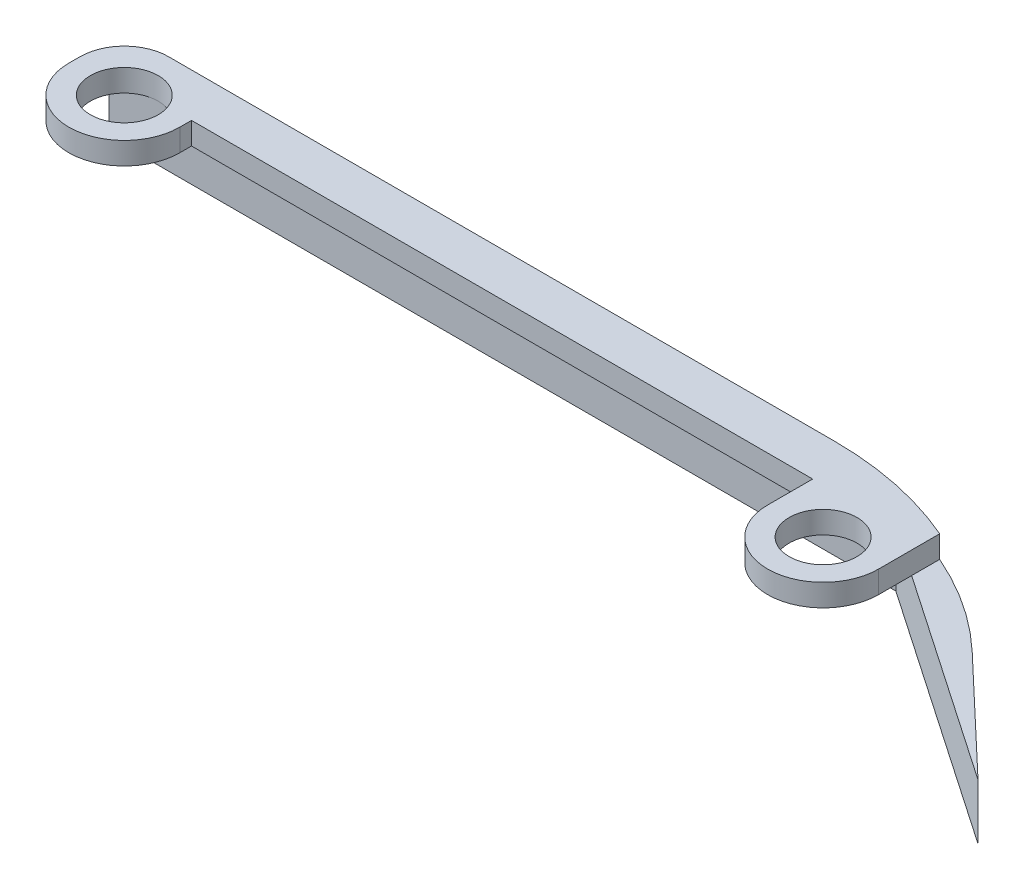
SolidWorks part; units mm, degrees
ref_plane "Front Plane" through (0, 0, 0) normal (0, 0, 1) x (1, 0, 0)
ref_plane "Top Plane" through (0, 0, 0) normal (0, 1, 0) x (1, 0, 0)
ref_plane "Right Plane" through (0, 0, 0) normal (1, 0, 0) x (0, 0, -1)
sketch "Sketch1" plane through (0, 0, 0) normal (0, 1, 0) x (1, 0, 0)
  line L2 (-5, 0) -> (-5, 5)
  line L5 (-5, 5) -> (71, 5)
  line L9 (71, -3) -> (71, 5)
  line L13 (5, 3.06) -> (61, 3.06)
  line L18 (61, -3) -> (61, 3.06)
  line L19 (5, 0) -> (5, 3.06)
  circle A6 centre (0, 0) radius 3.06
  arc A7 (-5, 0) -> (5, 0) centre (0, 0) ccw
  circle A8 centre (66, -3) radius 3.06
  arc A11 (61, -3) -> (71, -3) centre (66, -3) ccw
  dimension "D5" = 3
  dimension "D6" = 10
  dimension "D2" = 10
  dimension "D1" = 6.12
  dimension "D3" = 6.12
  dimension "D4" = 66
extrude "Boss-Extrude1" add sketch "Sketch1" along normal blind 2
sketch "Sketch4" plane through (0, 0, 0) normal (0, -1, 0) x (-1, 0, 0)
  line L0 (5, 5) -> (-71, 5)
  line L4 (-90, -13.0108) -> (-67, 1.4654) construction
  line L8 (-66.5, 3.06) -> (5, 3.06)
  line L9 (5, 5) -> (5, 0) construction
  line L10 (5, 3.06) -> (5, 5)
  line L12 (-71, 5) -> (-89.9333, -12.9688)
  line L13 (-89.9333, -12.9688) -> (-66.5, 3.06)
  circle A0 centre (-82, -14) radius 8 construction
  dimension "D1" = 4.5
extrude "Boss-Extrude3" add sketch "Sketch4" along normal blind 5
sketch "Sketch6" plane through (0, 2, 0) normal (0, 1, 0) x (1, 0, 0)
  line L0 (61, 3.06) -> (61, -3) construction
  line L1 (5, 3.06) -> (61, 3.06)
  line L2 (5, 3.06) -> (5, 1.06)
  line L3 (5, 1.06) -> (61, 1.06)
  line L4 (61, 3.06) -> (61, 1.06)
  dimension "D1" = 2
extrude "Boss-Extrude4" add sketch "Sketch6" against normal up to surface (2 mm away) up to face at (0, 0, -0.1867)
fillet "Fillet2" radius 30 2 edges at (71, 1, -5) (71, -2.5, -5)
fillet "Fillet3" radius 4 3 edges at (-5, -1.5, -5) (-5, -2.5, -3.06) (-5, -5, -4.03)
